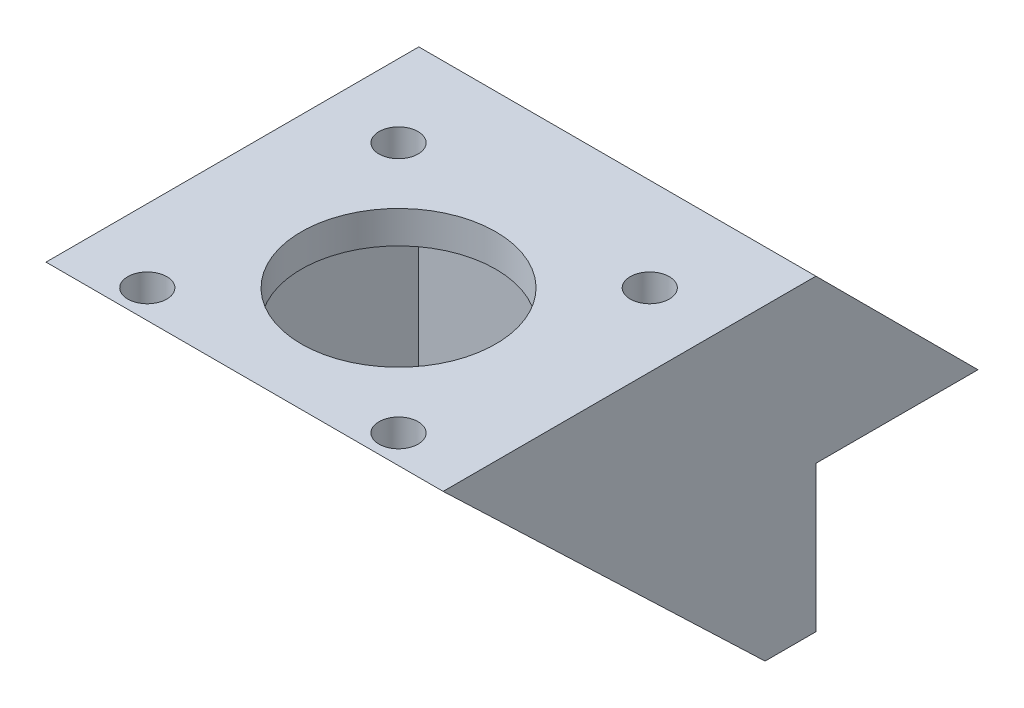
SolidWorks part; units mm, degrees
ref_plane "前基準面" through (0, 0, 0) normal (0, 0, 1) x (1, 0, 0)
ref_plane "上基準面" through (0, 0, 0) normal (0, 1, 0) x (1, 0, 0)
ref_plane "右基準面" through (0, 0, 0) normal (1, 0, 0) x (0, 0, -1)
sketch "草圖1" plane through (0, 0, 0) normal (0, 1, 0) x (1, 0, 0)
  line L1 (24.5, -33) -> (-24.5, -33)
  line L2 (24.5, -33) -> (24.5, 33)
  line L3 (24.5, 33) -> (-24.5, 33)
  line L4 (-24.5, -33) -> (-24.5, 33)
  line L5 (0, 33) -> (0, -33) construction
  line L6 (24.5, 0) -> (-24.5, 0) construction
  point P0 (0, 0)
  dimension "D1" = 66
  dimension "D2" = 49
extrude "填料-伸長1" add sketch "草圖1" along normal blind 44
sketch "草圖2" plane through (0, 0, 33) normal (0, 0, 1) x (1, 0, 0)
  line L1 (-20.511, 0) -> (21.489, 0)
  line L2 (-20.511, 0) -> (-20.511, 40)
  line L3 (-20.511, 40) -> (21.489, 40)
  line L4 (21.489, 0) -> (21.489, 40)
  dimension "D1" = 40
  dimension "D2" = 42
extrude "除料-伸長1" cut sketch "草圖2" against normal blind 42 contours L2 L1 L4 L3
sketch "草圖3" plane through (-24.5, 0, 0) normal (-1, 0, 0) x (0, 0, 1)
  line L0 (-13, 44) -> (-13, 0)
  line L1 (-33, 44) -> (33, 44) construction
  line L2 (-33, 44) -> (-33, 0) construction
  line L3 (-33, 0) -> (33, 0) construction
  line L4 (-33, 24) -> (-13, 24)
  line L5 (-33, 24) -> (-33, 0)
  line L6 (-13, 44) -> (-33, 24)
  line L7 (-33, 24) -> (-13, 24)
  line L8 (-33, 24) -> (-33, 0)
  line L9 (-33, 0) -> (-13, 0)
  line L10 (-13, 24) -> (-13, 0)
  line L11 (33, 44) -> (-13, 0)
  line M7 (-33, 0) -> (33, 0)
  line M8 (33, 0) -> (33, 44)
  line M9 (33, 44) -> (-33, 44)
  line M10 (-33, 44) -> (-33, 0)
  dimension "D1" = 20
  dimension "D2" = 20
extrude "除料-伸長2" cut sketch "草圖3" against normal blind 50 contours L6 M9 M10 | L4 L0 M10 M7 | L11 M8 M7 region at (-24.5, 37.3333, -26.3333) region at (-24.5, 12, -23) region at (-24.5, 14.6667, 17.6667)
sketch "草圖5" plane through (0, 44, 0) normal (0, 1, 0) x (1, 0, 0)
  line L0 (-24.5, -10) -> (24.5, -10)
  line L1 (-24.5, 13) -> (-24.5, -33) construction
  line L2 (24.5, -33) -> (24.5, 13) construction
  line L3 (0, 13) -> (0, -33)
  line L4 (24.5, 13) -> (-24.5, 13) construction
  line L5 (-24.5, -33) -> (24.5, -33) construction
  line L6 (0, 33) -> (0, 13) construction
  line L7 (24.5, 33) -> (-24.5, 33) construction
  line L8 (-24.5, 23) -> (24.5, 23) construction
  line L9 (-24.5, 13) -> (-24.5, 33) construction
  line L10 (24.5, 13) -> (24.5, 33) construction
  line L11 (0, -14) -> (25.4419, -14) construction
  circle A0 centre (0, -14) radius 12
  circle A1 centre (15.5, 1.5) radius 2.4083
  circle A5 centre (10.5, 23) radius 4.25
  circle A6 centre (-10.5, 23) radius 4.25
  circle A7 centre (15.5, -29.5) radius 2.4083
  circle A8 centre (-15.5, -29.5) radius 2.4083
  circle A9 centre (-15.5, 1.5) radius 2.4083
  circle A10 centre (10.5, 23) radius 5
  circle A12 centre (-10.5, 23) radius 5
  dimension "D1" = 24
  dimension "D2" = 8.5
  dimension "D5" = 10
  dimension "D3" = 15.5
  dimension "D4" = 21
  dimension "D6" = 27
extrude "除料-伸長3" cut sketch "草圖5" against normal blind 50 contours A1 | A0 | A6 | A5 | A7 | A8 | A9 region at (15.5, 44, -1.5)
sketch "草圖7" plane through (0, 44, 0) normal (0, 1, 0) x (1, 0, 0)
  line L0 (0, 33) -> (0, 13) construction
  line L1 (24.5, 33) -> (-24.5, 33) construction
  line L2 (24.5, 13) -> (-24.5, 13) construction
  circle A0 centre (10.5, 23) radius 5
  circle A1 centre (-10.5, 23) radius 5
  dimension "D1" = 10
extrude "除料-伸長4" cut sketch "草圖7" against normal blind 18
sketch "草圖8" plane through (0, 0, -13) normal (0, 0, -1) x (-1, 0, 0)
  line L0 (-24.5, 24) -> (-24.5, 0) construction
  line L1 (-24.5, 6) -> (24.5, 6)
  line L2 (-24.5, 6) -> (-24.5, 0)
  line L3 (-24.5, 0) -> (24.5, 0)
  line L4 (24.5, 6) -> (24.5, 0)
  dimension "D1" = 6
extrude "除料-伸長5" cut sketch "草圖8" against normal blind 18
